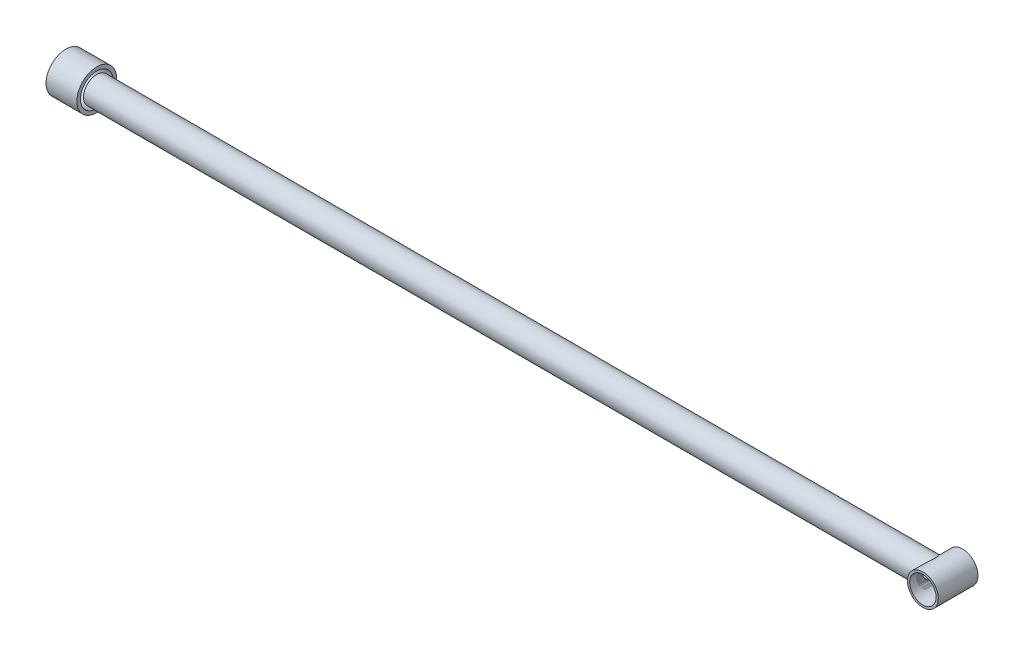
SolidWorks part; units mm, degrees
ref_plane "Front Plane" through (0, 0, 0) normal (0, 0, 1) x (1, 0, 0)
ref_plane "Top Plane" through (0, 0, 0) normal (0, 1, 0) x (1, 0, 0)
ref_plane "Right Plane" through (0, 0, 0) normal (1, 0, 0) x (0, 0, -1)
sketch "Sketch2" plane through (0, 0, 0) normal (1, 0, 0) x (0, 0, -1)
  circle A0 centre (0, 0) radius 75
  circle A1 centre (0, 0) radius 37.5
  dimension "D1" = 150
  dimension "D2" = 75
extrude "Boss-Extrude1" add sketch "Sketch2" along normal blind 4750
sketch "Sketch3" plane through (0, 0, 0) normal (-1, 0, 0) x (0, 0, 1)
  circle A0 centre (0, 0) radius 112.5
  circle A1 centre (0, 0) radius 92.5
  dimension "D1" = 225
  dimension "D2" = 185
extrude "Boss-Extrude2" add sketch "Sketch3" along normal blind 175
sketch "Sketch4" plane through (0, 0, 0) normal (0, 0, 1) x (1, 0, 0)
  circle A0 centre (4795.7962, 0) radius 87.5
  circle A1 centre (4795.7962, 0) radius 75
  dimension "D1" = 175
  dimension "D2" = 150
extrude "Boss-Extrude9" add sketch "Sketch4" along normal through all and the other way through all separate body
sketch "Sketch5" plane through (0, 0, 112.5) normal (0, 0, 1) x (1, 0, 0)
  circle A0 centre (4795.7962, 0) radius 75
extrude "Cut-Extrude1" cut sketch "Sketch5" against normal blind 175
sketch "Sketch6" plane through (0, 0, 0) normal (-1, 0, 0) x (0, 0, 1)
  circle A0 centre (0, 0) radius 37.5
extrude "Cut-Extrude2" cut sketch "Sketch6" against normal blind 4787
